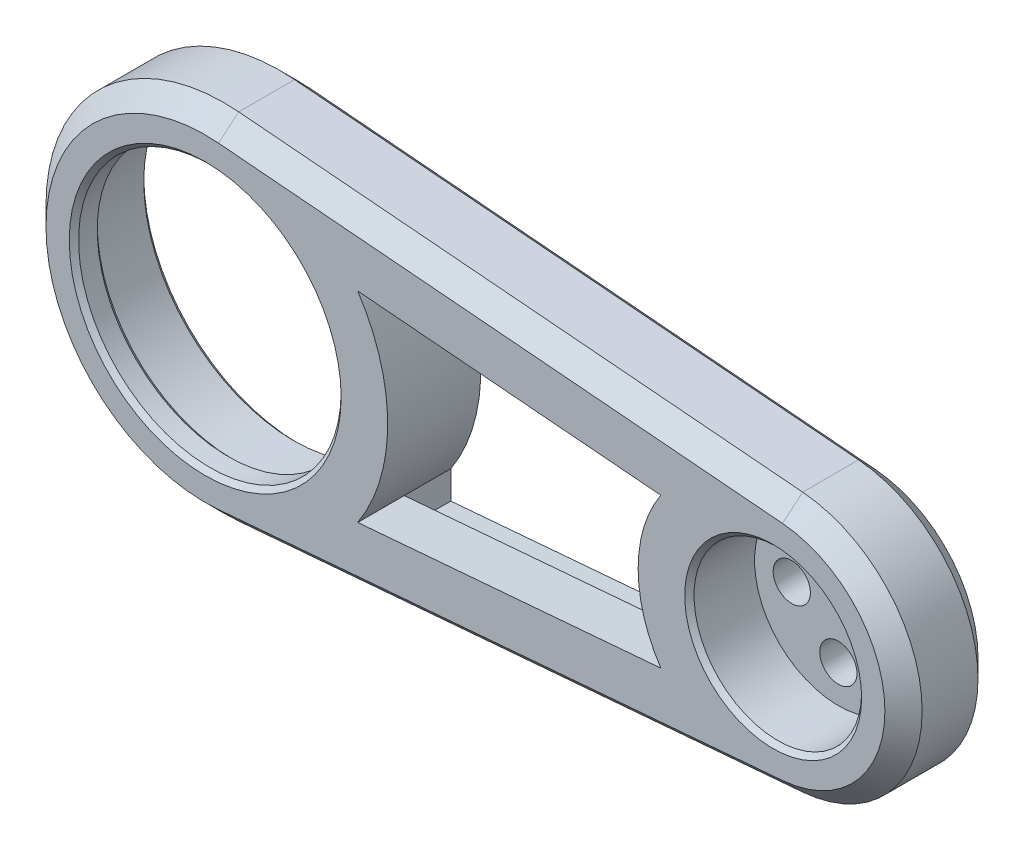
SolidWorks part; units mm, degrees
material "PEI"
ref_plane "前视基准面" through (0, 0, 0) normal (0, 0, 1) x (1, 0, 0)
ref_plane "上视基准面" through (0, 0, 0) normal (0, 1, 0) x (1, 0, 0)
ref_plane "右视基准面" through (0, 0, 0) normal (1, 0, 0) x (0, 0, -1)
other "Configuration Table"
sketch "草图2" plane through (0, 0, 0) normal (0, 0, 1) x (1, 0, 0)
  line L0 (0, 0) -> (61, 0) construction
  line L1 (1.5969, 19.0331) -> (62.1705, 13.951)
  line L2 (1.5969, -19.0331) -> (62.1705, -13.951)
  circle A0 centre (61, 0) radius 9
  circle A1 centre (61, 0) radius 14
  circle A2 centre (0, 0) radius 16.1
  circle A3 centre (0, 0) radius 19.1
  dimension "D1" = 18
  dimension "D2" = 28
  dimension "D4" = 32.2
  dimension "D3" = 61
  dimension "D5" = 3
extrude "凸台-拉伸1" add sketch "草图2" against normal blind 7 contours A2 A3 | A3 L0 A1 L1 | L0 A3 L2 A1 | A1 A0 region at (13.6613, -12.5632, 0) region at (32.3346, 9.1539, 0) region at (32.3346, -9.1539, 0) region at (51.7914, 10.0136, 0)
sketch "草图3" plane through (0, 0, -7) normal (0, 0, -1) x (-1, 0, 0)
  line L2 (-62.1705, -13.951) -> (-1.5969, -19.0331)
  line L3 (-1.5969, 19.0331) -> (-62.1705, 13.951)
  line L4 (-62.1705, -13.951) -> (-1.5969, -19.0331)
  line L5 (-1.5969, 19.0331) -> (-62.1705, 13.951)
  circle A0 centre (-61, 0) radius 9 construction
  circle A1 centre (-61, 0) radius 9
  arc A2 (-1.5969, -19.0331) -> (-1.5969, 19.0331) centre (0, 0) ccw
  arc A3 (-62.1705, 13.951) -> (-62.1705, -13.951) centre (-61, 0) ccw
  arc A4 (-1.5969, -19.0331) -> (-1.5969, 19.0331) centre (0, 0) ccw
  arc A5 (-62.1705, 13.951) -> (-62.1705, -13.951) centre (-61, 0) ccw
  circle A6 centre (0, 0) radius 16.1 construction
  circle A7 centre (0, 0) radius 16.1
  line M5 (-62.1705, -13.951) -> (-1.5969, -19.0331)
  arc M6 (-1.5969, -19.0331) -> (-1.5969, 19.0331) centre (0, 0) ccw
  line M7 (-1.5969, 19.0331) -> (-62.1705, 13.951)
  arc M8 (-62.1705, 13.951) -> (-62.1705, -13.951) centre (-61, 0) ccw
  circle M9 centre (0, 0) radius 16.1
  circle M10 centre (-61, 0) radius 9
  dimension "D1" = 0
extrude "凸台-拉伸2" add sketch "草图3" along normal blind 3 contours M10 | M8 M5 M6 M7 M9 M10 region at (32.1329, 0, -7) region at (61, 0, -7)
sketch "草图4" plane through (0, 0, 0) normal (0, 0, 1) x (1, 0, 0)
  circle A0 centre (0, 0) radius 16.1 construction
  circle A1 centre (0, 0) radius 16.1
  circle A2 centre (0, 0) radius 14.1
  dimension "D1" = 2
extrude "凸台-拉伸3" add sketch "草图4" against normal blind 3
chamfer "倒角1" distance 0.5 angle 45 4 edges at (70, 0, 0) (-16.1, 0, -10) (14.1, 0, -3) (14.1, 0, 0)
chamfer "倒角2" distance 2 angle 45 8 edges at (31.8837, -16.4921, -10) (-19.1, 0, -10) (75, 0, -10) (31.8837, 16.4921, -10) (31.8837, -16.4921, 0) (-19.1, 0, 0) (75, 0, 0) (31.8837, 16.4921, 0)
sketch "草图5" plane through (0, 0, -10) normal (0, 0, -1) x (-1, 0, 0)
  line L0 (-85.5329, 0) -> (49.23, 0) construction
  line L1 (-61, 18.9424) -> (-61, -22.3961) construction
  circle A0 centre (-61, 0) radius 5 construction
  circle A1 centre (-61, 0) radius 9
  circle A2 centre (-61, 0) radius 9
  circle A3 centre (-61, 5) radius 2
  circle A4 centre (-56, 0) radius 2
  circle A5 centre (-61, -5) radius 2
  circle A6 centre (-66, 0) radius 2
  dimension "D2" = 10
  dimension "D3" = 4
  dimension "D1" = 0
  dimension "D4" = 4
extrude "切除-拉伸1" cut sketch "草图5" against normal up to surface (3 mm away) contours A3 | A6 | A5 | A4 region at (61, 5, -10) region at (56, 0, -10) region at (61, -5, -10) region at (66, 0, -10) up to face at (70, 0, -7)
sketch "草图6" plane through (0, 0, 0) normal (0, 0, 1) x (1, 0, 0)
  line L0 (61.5852, 6.9755) -> (1.0116, 12.0576)
  line L1 (1.0116, -12.0576) -> (61.5852, -6.9755)
  line L2 (1.4297, -17.0401) -> (62.0033, -11.958)
  line L3 (62.0033, 11.958) -> (1.4297, 17.0401)
  line L4 (1.4297, -17.0401) -> (62.0033, -11.958)
  line L5 (62.0033, 11.958) -> (1.4297, 17.0401)
  circle A0 centre (0, 0) radius 14.6 construction
  circle A1 centre (0, 0) radius 14.6
  arc A2 (1.4297, 17.0401) -> (1.4297, -17.0401) centre (0, 0) ccw
  arc A3 (62.0033, -11.958) -> (62.0033, 11.958) centre (61, 0) ccw
  arc A4 (1.4297, 17.0401) -> (1.4297, -17.0401) centre (0, 0) ccw
  arc A5 (62.0033, -11.958) -> (62.0033, 11.958) centre (61, 0) ccw
  circle A6 centre (61, 0) radius 9.5 construction
  circle A7 centre (61, 0) radius 9.5
  arc A9 (1.0116, 12.0576) -> (1.0116, -12.0576) centre (0, 0) ccw
  arc A10 (61.5852, -6.9755) -> (61.5852, 6.9755) centre (61, 0) ccw
  circle A12 centre (0, 0) radius 19.6
  circle A13 centre (61, 0) radius 14.5
  dimension "D1" = 0
  dimension "D2" = 5
  dimension "D3" = 5
extrude "切除-拉伸2" cut sketch "草图6" against normal up to surface (10 mm away) contours A13 L0 A12 L1 region at (32.3147, 0, 0) up to face at (59, 5, -10)
sketch "草图7" plane through (0, 0, -10) normal (0, 0, -1) x (-1, 0, 0)
  line L0 (-16.3768, -10.7685) -> (-48.9313, -8.0372) construction
  line L1 (-48.9313, 8.0372) -> (-16.3768, 10.7685) construction
  line L2 (-16.3768, -10.7685) -> (-48.9313, -8.0372)
  line L3 (-48.9313, 8.0372) -> (-16.3768, 10.7685)
  line L4 (-48.9313, 11.0477) -> (-16.3768, 13.779)
  line L5 (-48.9313, -11.0477) -> (-16.3768, -13.779)
  line L6 (-48.9313, -11.0477) -> (-48.9313, -8.0372)
  line L7 (-16.3768, -13.779) -> (-16.3768, -10.7685)
  line L8 (-16.3768, 13.779) -> (-16.3768, 10.7685)
  line L9 (-48.9313, 11.0477) -> (-48.9313, 8.0372)
  line M5 (-48.9313, 8.0372) -> (-16.3768, 10.7685)
  line M7 (-16.3768, -10.7685) -> (-48.9313, -8.0372)
  dimension "D1" = 3
  dimension "D2" = 3
extrude "切除-拉伸3" cut sketch "草图7" against normal blind 5 contours L4 L9 L8 M5 | L5 L7 L6 M7 region at (32.654, -10.9081, -10) region at (32.654, 10.9081, -10)
equation "\"D3@草图2\"= \"从动杆_前_长度\""
equation "\"从动杆_前_长度\"= 61"
